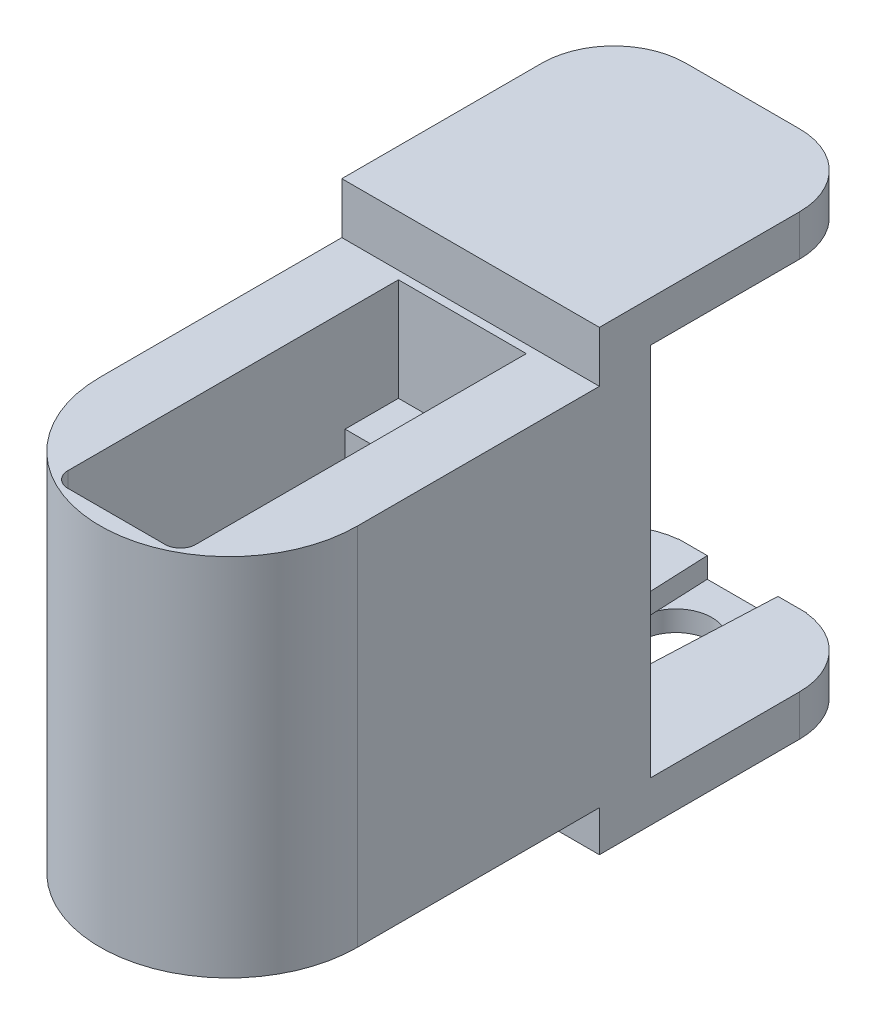
SolidWorks part; units mm, degrees
ref_plane "Front Plane" through (0, 0, 0) normal (0, 0, 1) x (1, 0, 0)
ref_plane "Top Plane" through (0, 0, 0) normal (0, 1, 0) x (1, 0, 0)
ref_plane "Right Plane" through (0, 0, 0) normal (1, 0, 0) x (0, 0, -1)
sketch "Sketch4" plane through (0, 0, 0) normal (0, 0, 1) x (1, 0, 0)
  line L1 (-6.23, -9.975) -> (6.23, -9.975)
  line L2 (-6.23, -9.975) -> (-6.23, 7.275)
  line L3 (-6.23, 7.275) -> (6.23, 7.275)
  line L4 (6.23, -9.975) -> (6.23, 7.275)
  point P4 (0, 7.275)
  dimension "D1" = 12.46
  dimension "D2" = 17.25
  dimension "D3" = 9.975
extrude "Boss-Extrude3" add sketch "Sketch4" along normal blind 6
sketch "Sketch8" plane through (0, -9.975, 0) normal (0, -1, 0) x (-1, 0, 0)
  circle A0 centre (0, -23.55) radius 12.5468
  circle A1 centre (0, -23.55) radius 11.15
  dimension "D1" = 22.3
  dimension "D2" = 23.55
extrude "Boss-Extrude6" add sketch "Sketch8" along normal blind 8.3 and the other way up to surface (17.25 mm away) other way up to face at (0, 7.275, 3)
sketch "Sketch5" plane through (0, 7.275, 0) normal (0, 1, 0) x (1, 0, 0)
  line L8 (12.5468, -23.55) -> (12.5468, 0)
  line L9 (12.5468, 0) -> (6.23, 0)
  line L10 (-12.5468, -23.55) -> (-12.5468, 0)
  line L11 (-12.5468, 0) -> (-6.23, 0)
  line L12 (-6.23, 0) -> (-6.23, -29.7)
  line L14 (6.23, -29.7) -> (6.23, 0)
  line L15 (-6.23, -29.7) -> (6.23, -29.7)
  line L16 (6.23, -6) -> (-6.23, -6) construction
  circle A0 centre (0, -23.55) radius 12.5468 construction
  arc A1 (-12.5468, -23.55) -> (12.5468, -23.55) centre (0, -23.55) ccw
  dimension "D1" = 23.7
  dimension "D2" = 23.55
extrude "Boss-Extrude4" add sketch "Sketch5" against normal up to surface (17.25 mm away) up to face at (0, -9.975, 3)
sketch "Sketch6" plane through (0, 7.275, 0) normal (0, 1, 0) x (1, 0, 0)
  line L0 (6.23, -6) -> (-6.23, -6) construction
  line L3 (6.23, -29.7) -> (-6.23, -29.7) construction
  circle A0 centre (0, -3.6) radius 0.75
  circle A1 centre (0, -32.1) radius 0.75
  dimension "D1" = 1.5
  dimension "D3" = 1.5
  dimension "D2" = 2.4
  dimension "D4" = 2.4
extrude "Cut-Extrude1" cut sketch "Sketch6" against normal blind 5
chamfer "Chamfer1" distance 0.5 angle 60 2 edges at (0, 7.275, 4.35) (0, 7.275, 32.85) first distance on face at (0, 7.275, 4.35)
sketch "Sketch10" plane through (0, 7.275, 0) normal (0, 1, 0) x (1, 0, 0)
  line L1 (-6.23, -6) -> (6.23, -6)
  line L2 (-6.23, -6) -> (-6.23, -29.7)
  line L3 (-6.23, -29.7) -> (6.23, -29.7)
  line L4 (6.23, -6) -> (6.23, -29.7)
extrude "Cut-Extrude3" cut sketch "Sketch10" against normal up to surface (17.25 mm away) up to face at (0, -9.975, 10.3399)
ref_plane "Plane1" through (0, 0, 36.0968) normal (0, 0, 1) x (1, 0, 0)
sketch "Sketch13" plane through (0, -18.275, 0) normal (0, -1, 0) x (1, 0, 0)
  line L0 (-12.5468, 23.55) -> (-12.5468, 0)
  line L1 (-12.5468, 0) -> (12.5468, 0)
  line L2 (12.5468, 0) -> (12.5468, 23.55)
  arc A0 (-12.5468, 23.55) -> (12.5468, 23.55) centre (0, 23.55) ccw
  point P3 (0, 0)
extrude "Boss-Extrude7" add sketch "Sketch13" against normal up to surface (8.3 mm away) up to face at (0, -9.975, 10.3399)
sketch "Sketch15" plane through (0, 7.275, 0) normal (0, 1, 0) x (1, 0, 0)
  line L0 (-12.5468, 0) -> (12.5468, 0)
  line L1 (12.5468, 0) -> (12.5468, -23.55)
  line L2 (-12.5468, 0) -> (-12.5468, -23.55)
  line L3 (6.23, -6) -> (6.23, -29.7) construction
  line L4 (-6.23, -0.8) -> (6.23, -0.8)
  line L5 (-6.23, -0.8) -> (-6.23, -33)
  line L6 (-4.73, -34.5) -> (4.73, -34.5)
  line L7 (6.23, -0.8) -> (6.23, -33)
  arc A0 (-12.5468, -23.55) -> (12.5468, -23.55) centre (0, -23.55) ccw
  circle A1 centre (0, -3.6) radius 0.75 construction
  arc A2 (4.73, -34.5) -> (6.23, -33) centre (4.73, -33) ccw
  arc A3 (-6.23, -33) -> (-4.73, -34.5) centre (-4.73, -33) ccw
  point P15 (0, -0.8)
  dimension "D1" = 0.8
  dimension "D3" = 1.5
  dimension "D2" = 2.8
  dimension "D4" = 0
  dimension "D5" = 34.5
extrude "Boss-Extrude9" add sketch "Sketch15" along normal blind 10
sketch "Sketch20" plane through (0, -18.275, 0) normal (0, -1, 0) x (1, 0, 0)
  circle A0 centre (0, 23.55) radius 7.15
  circle A1 centre (0, 23.55) radius 11.15
  circle A2 centre (0, 23.55) radius 11.15 construction
  dimension "D1" = 14.3
extrude "Boss-Extrude11" add sketch "Sketch20" against normal up to surface (8.3 mm away) up to face at (0, -9.975, 27.1007)
sketch "Sketch21" plane through (0, -18.275, 0) normal (0, -1, 0) x (1, 0, 0)
  circle A0 centre (0, 23.55) radius 7.15
  circle A1 centre (0, 23.55) radius 10.15
  circle A2 centre (0, 23.55) radius 7.15 construction
  dimension "D1" = 20.3
extrude "Cut-Extrude7" cut sketch "Sketch21" against normal blind 1.3
sketch "Sketch11" plane through (0, 0, 29.7) normal (0, 0, 1) x (1, 0, 0)
  line L1 (-5, -9.975) -> (5, -9.975)
  line L2 (-5, -9.975) -> (-5, -11.975)
  line L3 (-5, -11.975) -> (5, -11.975)
  line L4 (5, -9.975) -> (5, -11.975)
  line L5 (3.6469, -9.975) -> (6.23, -9.975) construction
  point P4 (0, -9.975)
  dimension "D1" = 0
  dimension "D2" = 10
  dimension "D3" = 2
extrude "Cut-Extrude4" cut sketch "Sketch11" against normal up to surface (23.7 mm away) up to face at (0, -1.35, 6)
sketch "Sketch24" plane through (0, -18.275, 0) normal (0, -1, 0) x (1, 0, 0)
  line L0 (6.23, 20.0415) -> (6.23, 6) construction
  line L1 (-6.23, 6) -> (6.23, 6)
  line L2 (-6.23, 6) -> (-6.23, 12)
  line L3 (-6.23, 12) -> (6.23, 12)
  line L4 (6.23, 6) -> (6.23, 12)
  dimension "D1" = 6
extrude "Cut-Extrude8" cut sketch "Sketch24" against normal up to next
sketch "Sketch17" plane through (-12.5468, 4.7282, 0) normal (1, 0, 0) x (0, -1, 0)
  line L0 (26.9782, 26.5) -> (26.9782, 0)
  line L1 (26.9782, 0) -> (-17.5218, 0)
  line L2 (-17.5218, 0) -> (-17.5218, 26.5)
  line L3 (-17.5218, 26.5) -> (-13.5218, 26.5)
  line L4 (-13.5218, 26.5) -> (-13.5218, 5)
  line L5 (-13.5218, 5) -> (22.9782, 5)
  line L6 (22.9782, 5) -> (22.9782, 26.5)
  line L7 (22.9782, 26.5) -> (26.9782, 26.5)
  point P2 (4.7282, 5)
  point P10 (4.7282, 0)
  dimension "D1" = 4
  dimension "D2" = 36.5
  dimension "D3" = 0
  dimension "D4" = 26.5
  dimension "D5" = 5
extrude "Boss-Extrude10" add sketch "Sketch17" along normal up to surface (25.0936 mm away) up to face at (12.5468, -0.5, 11.775)
sketch "Sketch18" plane through (0, -18.25, 0) normal (0, 1, 0) x (0, 0, 1)
  line L0 (-26.5, -12.5468) -> (-26.5, 12.5468) construction
  line L1 (-26.5, 6.2191) -> (-5, 6.2191)
  line L2 (-26.5, 6.2191) -> (-26.5, -6.2191)
  line L3 (-26.5, -6.2191) -> (-5, -6.2191)
  line L4 (-5, 6.2191) -> (-5, -6.2191)
  line L5 (-5, -12.5468) -> (-5, 12.5468) construction
  point P6 (-26.5, 0)
  point P7 (-26.5, 0)
  dimension "D1" = 0
extrude "Cut-Extrude5" cut sketch "Sketch18" against normal blind 2
sketch "Sketch19" plane through (0, -20.25, 0) normal (0, 1, 0) x (0, 0, 1)
  line L0 (-26.5, -12.5468) -> (-26.5, 12.5468) construction
  line L1 (-26.5, 12.5468) -> (-26.5, -12.5468) construction
  circle A0 centre (-20, 0) radius 3.5
  point P8 (-26.5, 0)
  dimension "D1" = 7
  dimension "D2" = 6.5
extrude "Cut-Extrude6" cut sketch "Sketch19" against normal through all both and the other way through all
fillet "Fillet1" radius 7 4 edges at (12.5468, -20.25, -26.5) (-12.5468, -20.25, -26.5) (-12.5468, 20.25, -26.5) (12.5468, 20.25, -26.5)
ref_plane "Plane2" through (0, 0, 0) normal (1, 0, 0) x (0, 0, -1)
ref_plane "Plane3" through (0, -0.5, 0) normal (0, -1, 0) x (-1, 0, 0)
sketch "Sketch22" plane through (0, 22.25, 0) normal (0, 1, 0) x (1, 0, 0)
  circle A0 centre (0, 20) radius 6.5
  dimension "D1" = 13
extrude "Boss-Extrude12" add sketch "Sketch22" against normal blind 5
sketch "Sketch23" plane through (0, 17.25, 0) normal (0, -1, 0) x (1, 0, 0)
  circle A0 centre (0, -20) radius 6.075
  dimension "D1" = 12.15
extrude "Boss-Extrude13" add sketch "Sketch23" along normal blind 5
fillet "Fillet2" radius 1 1 edges at (0, 12.25, -26.075)
sketch "Sketch25" plane through (0, -20.25, 0) normal (0, 1, 0) x (1, 0, 0)
  line L0 (-6.2191, 5) -> (-2.5, 5)
  line L1 (12.5468, 5) -> (-12.5468, 5) construction
  line L2 (-2.5, 5) -> (-3.1585, 20)
  line L3 (-3.1585, 20) -> (-3.4438, 26.5)
  line L4 (-3.4438, 26.5) -> (-6.2191, 26.5)
  line L5 (-6.2191, 26.4676) -> (-6.2191, 5) construction
  line L6 (-6.2191, 26.5) -> (-6.2191, 5)
  line L7 (6.2191, 5) -> (2.5, 5)
  line L8 (2.5, 5) -> (3.1585, 20)
  line L9 (3.1585, 20) -> (3.4438, 26.5)
  line L10 (3.4438, 26.5) -> (6.2191, 26.5)
  line L11 (6.2191, 5) -> (6.2191, 26.4676) construction
  line L12 (6.2191, 26.5) -> (6.2191, 5)
  line L13 (0, -23.6775) -> (0, 23.6775) construction
  line L14 (5.5468, 26.5) -> (-5.5468, 26.5) construction
  circle A0 centre (0, 20) radius 3.5 construction
  point P18 (5.0288, 12.153)
  point P19 (3.1965, 10.3207)
  point P20 (-3.7449, 8.6294)
  point P21 (-2.864, 5)
  point P22 (0, 0)
  point P23 (0, 0)
  point P25 (0.0253, 3.8373)
  point P27 (0, 0)
  point P28 (0, 0)
  point P29 (-1.1938, 7.9775)
  dimension "D1" = 5
  dimension "D2" = 2.5
  dimension "D3" = 3.1585
  dimension "D4" = 6.317
  dimension "D5" = 0
  dimension "D6" = 0
extrude "Boss-Extrude15" add sketch "Sketch25" along normal up to surface (2 mm away) up to face at (9.7194, -18.25, -14.2975)
sketch "Sketch26" plane through (0, -22.25, 0) normal (0, -1, 0) x (-1, 0, 0)
  circle A0 centre (0, 10) radius 0.75
  circle A1 centre (0, 20) radius 3.5 construction
  dimension "D1" = 1.5
  dimension "D2" = 10
  dimension "D3" = 0
extrude "Cut-Extrude9" cut sketch "Sketch26" against normal up to next
